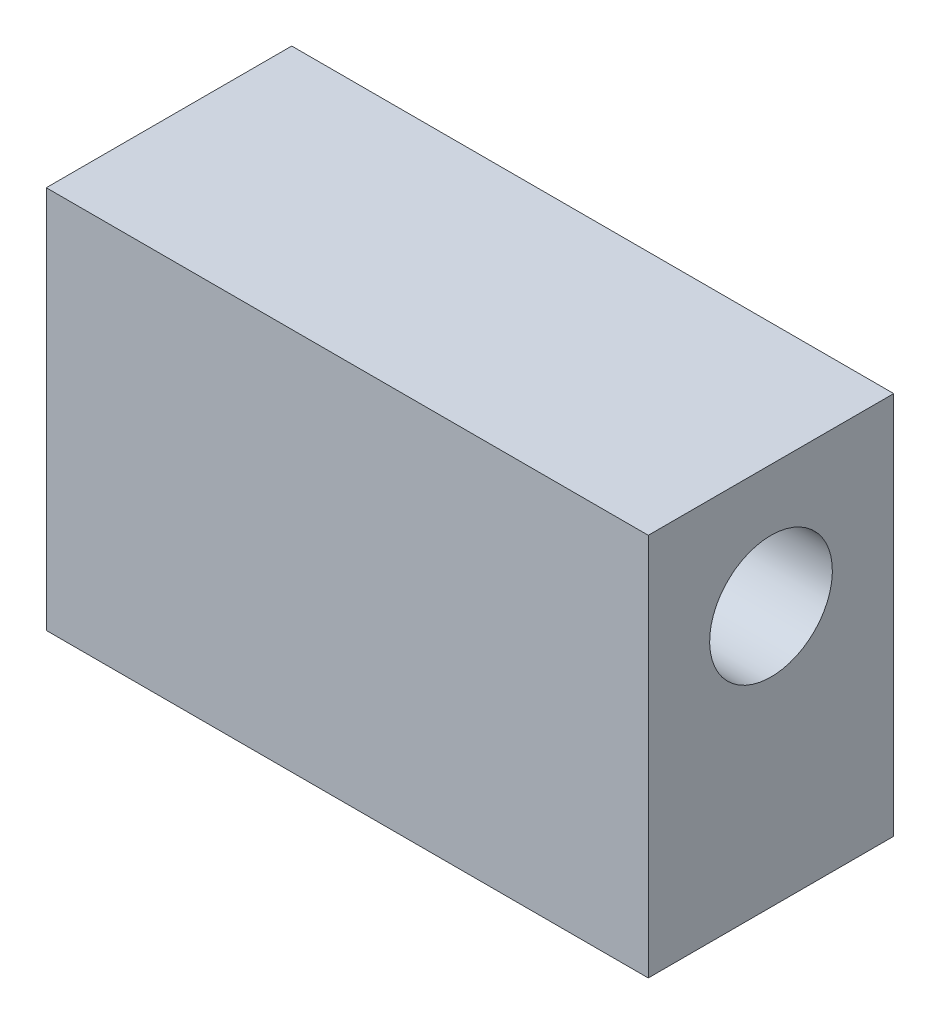
SolidWorks part; units mm, degrees
ref_plane "Front" through (0, 0, 0) normal (0, 0, 1) x (1, 0, 0)
ref_plane "Top" through (0, 0, 0) normal (0, 1, 0) x (1, 0, 0)
ref_plane "Right" through (0, 0, 0) normal (1, 0, 0) x (0, 0, -1)
sketch "Sketch3" plane through (0, 0, 0) normal (0, 0, 1) x (1, 0, 0)
  line L0 (-0.127, -6.35) -> (30.1755, -6.35)
  line L1 (0, 0) -> (31.1484, 0)
  line L2 (0, 0) -> (0, -19.8376)
  line L3 (0, -19.8376) -> (31.1484, -19.8376)
  line L4 (31.1484, 0) -> (31.1484, -19.8376)
  line L5 (15.5742, -19.8376) -> (15.5742, 0) construction
  line L6 (15.5742, -6.35) -> (8.0621, -19.3614) construction
  line L15 (12.5496, -11.5887) -> (15.5742, -13.335) construction
  line L16 (15.5742, -6.35) -> (22.9274, -19.0862) construction
  circle A0 centre (15.5742, -6.35) radius 6.0492 construction
  point P14 (0, -6.35)
  point P17 (9.525, -6.35)
  point P19 (31.1484, -6.35)
  point P20 (7.7871, -19.8376)
  point P21 (0, 0)
  point P22 (0, 0)
  point P23 (0, 0)
  point P24 (23.3613, -19.8376)
  point P25 (0, 0)
  dimension "D2" = 6.35
  dimension "D6" = 3.4925
  dimension "D3" = 60
  dimension "D1" = 9.525
  dimension "D4" = 9.525
  dimension "D5" = 60
extrude "Boss-Extrude1" add sketch "Sketch3" along normal mid plane 12.7
sketch "Sketch4" plane through (0, 0, 0) normal (-1, 0, 0) x (0, 0, 1)
  circle A0 centre (0, -6.35) radius 3.175
  point P2 (-0.9673, -12.4552)
  point P3 (0, 0)
  point P5 (0, 0)
  dimension "D1" = 6.35
extrude "Cut-Extrude1" cut sketch "Sketch4" against normal blind 9.525
ref_plane "Plane1" through (7.7871, -19.8376, 0) normal (-0.5, -0.866, 0) x (-0.866, 0.5, 0)
ref_plane "Mirror Plane" through (15.5742, 0, 0) normal (-1, 0, 0) x (0, 0, 1)
sketch "Sketch5" plane through (7.7871, -19.8376, 0) normal (-0.5, -0.866, 0) x (-0.866, 0.5, 0)
  circle A0 centre (0, 0) radius 3.175
  dimension "D1" = 6.35
extrude "Cut-Extrude5" cut sketch "Sketch5" against normal blind 9.525 and the other way up to next
mirror "Mirror1" about plane through (15.5742, 0, 0) normal (-1, 0, 0) of "Cut-Extrude5", "Cut-Extrude1"
sketch "Sketch6" plane through (0, 0, -6.35) normal (0, 0, -1) x (-1, 0, 0)
  circle A0 centre (-15.5742, -6.35) radius 3.175
  point P2 (0, 0)
  dimension "D1" = 6.35
extrude "Cut-Extrude6" cut sketch "Sketch6" against normal blind 9.525
equation "\"truss_member_od\" = .25in"
equation "\"truss_member_id\" = 0in"
equation "\"truss_member_L1\" = 2.75in"
equation "\"connector_hole_depth\" = .375in"
equation "\"D1@Boss-Extrude1\"=\"truss_member_od\"*2"
equation "\"D6@Sketch3\"=\"truss_member_od\"/2*1.1"
equation "\"D1@Sketch4\"=\"truss_member_od\""
equation "\"D1@Cut-Extrude1\"=\"connector_hole_depth\""
equation "\"D1@Sketch3\"=\"connector_hole_depth\""
equation "\"D4@Sketch3\"=\"connector_hole_depth\""
equation "\"D1@Sketch5\"=\"truss_member_od\""
equation "\"D1@Cut-Extrude5\"=\"connector_hole_depth\""
equation "\"D1@Cut-Extrude6\"=\"connector_hole_depth\""
equation "\"D1@Sketch6\"=\"truss_member_od\""
